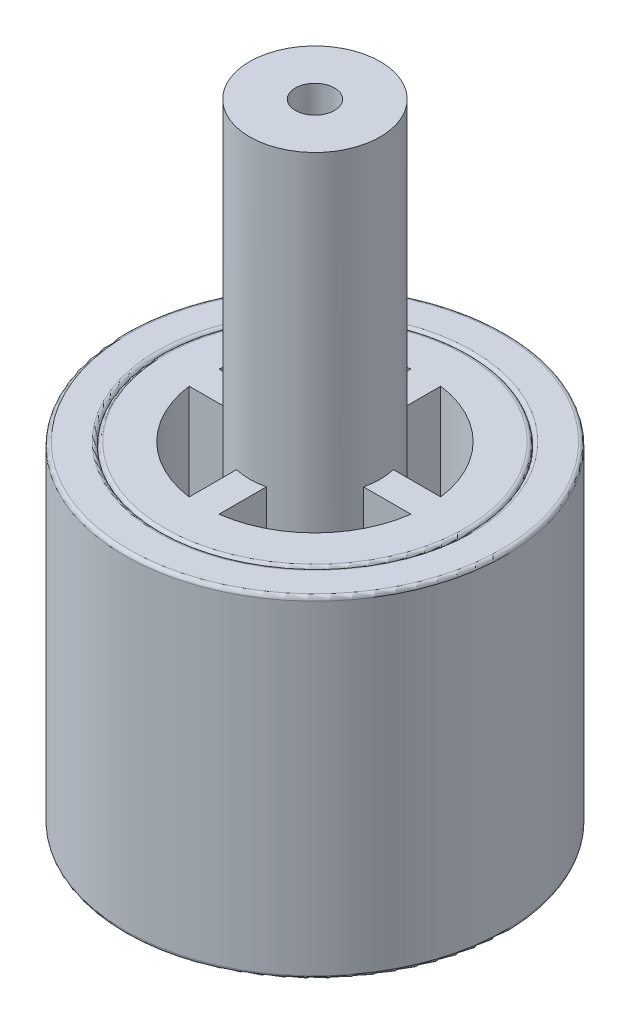
SolidWorks part; units mm, degrees
material "Полиамид ПА-6Б ТУ 6-05-988-93"
ref_plane "Спереди" through (0, 0, 0) normal (0, 0, 1) x (1, 0, 0)
ref_plane "Сверху" through (0, 0, 0) normal (0, 1, 0) x (1, 0, 0)
ref_plane "Справа" through (0, 0, 0) normal (1, 0, 0) x (0, 0, -1)
sketch "Эскиз1" plane through (0, 0, 0) normal (0, 1, 0) x (1, 0, 0)
  circle A0 centre (0, 0) radius 4.125
  dimension "D1" = 8.25
extrude "Бобышка-Вытянуть1" add sketch "Эскиз1" along normal blind 8.9
sketch "Эскиз2" plane through (0, 8.9, 0) normal (0, 1, 0) x (1, 0, 0)
  circle A0 centre (0, 0) radius 1.75
  dimension "D1" = 3.5
extrude "Бобышка-Вытянуть2" add sketch "Эскиз2" along normal blind 7.95
sketch "Эскиз3" plane through (0, 8.9, 0) normal (0, 1, 0) x (1, 0, 0)
  line L0 (-0.4, 2.9732) -> (-0.4, 1.7037)
  line L1 (-2.9732, 0.4) -> (-1.7037, 0.4)
  line L2 (-2.9732, -0.4) -> (-1.7037, -0.4)
  line L3 (0.4, 2.9732) -> (0.4, 1.7037)
  line L5 (1.7037, 0.4) -> (2.9732, 0.4)
  line L6 (1.7037, -0.4) -> (2.9732, -0.4)
  line L7 (0.4, -1.7037) -> (0.4, -2.9732)
  line L8 (-0.4, -1.7037) -> (-0.4, -2.9732)
  circle A0 centre (0, 0) radius 1.75 construction
  arc A1 (-0.4, 1.7037) -> (-1.7037, 0.4) centre (0, 0) ccw
  arc A2 (-0.4, 2.9732) -> (-2.9732, 0.4) centre (0, 0) ccw
  arc A3 (-1.7037, -0.4) -> (-0.4, -1.7037) centre (0, 0) ccw
  arc A4 (-2.9732, -0.4) -> (-0.4, -2.9732) centre (0, 0) ccw
  arc A5 (0.4, -1.7037) -> (1.7037, -0.4) centre (0, 0) ccw
  arc A6 (0.4, -2.9732) -> (2.9732, -0.4) centre (0, 0) ccw
  arc A7 (1.7037, 0.4) -> (0.4, 1.7037) centre (0, 0) ccw
  arc A8 (2.9732, 0.4) -> (0.4, 2.9732) centre (0, 0) ccw
  dimension "D1" = 6
  dimension "D2" = 0.4
  dimension "D3" = 0.8
  dimension "D4" = 0.4
  dimension "D5" = 0.8
extrude "Вырез-Вытянуть1" cut sketch "Эскиз3" against normal blind 3
sketch "Эскиз4" plane through (0, 0, 0) normal (0, -1, 0) x (1, 0, 0)
  line L2 (0.4, -1.7037) -> (0.4, -2.9732)
  line L3 (2.9732, -0.4) -> (1.7037, -0.4)
  line L4 (0.4, -1.7037) -> (0.4, -2.9732)
  line L5 (2.9732, -0.4) -> (1.7037, -0.4)
  line L6 (0.4, 2.9732) -> (0.4, 1.7037)
  line L7 (1.7037, 0.4) -> (2.9732, 0.4)
  line L8 (0.4, 2.9732) -> (0.4, 1.7037)
  line L9 (1.7037, 0.4) -> (2.9732, 0.4)
  line L10 (-2.9732, 0.4) -> (-1.7037, 0.4)
  line L11 (-0.4, 1.7037) -> (-0.4, 2.9732)
  line L12 (-2.9732, 0.4) -> (-1.7037, 0.4)
  line L13 (-0.4, 1.7037) -> (-0.4, 2.9732)
  line L14 (-1.7037, -0.4) -> (-2.9732, -0.4)
  line L15 (-0.4, -2.9732) -> (-0.4, -1.7037)
  line L16 (-1.7037, -0.4) -> (-2.9732, -0.4)
  line L17 (-0.4, -2.9732) -> (-0.4, -1.7037)
  arc A2 (0.4, -1.7037) -> (1.7037, -0.4) centre (0, 0) ccw
  arc A3 (0.4, -2.9732) -> (2.9732, -0.4) centre (0, 0) ccw
  arc A4 (0.4, -1.7037) -> (1.7037, -0.4) centre (0, 0) ccw
  arc A5 (0.4, -2.9732) -> (2.9732, -0.4) centre (0, 0) ccw
  arc A6 (2.9732, 0.4) -> (0.4, 2.9732) centre (0, 0) ccw
  arc A7 (1.7037, 0.4) -> (0.4, 1.7037) centre (0, 0) ccw
  arc A8 (2.9732, 0.4) -> (0.4, 2.9732) centre (0, 0) ccw
  arc A9 (1.7037, 0.4) -> (0.4, 1.7037) centre (0, 0) ccw
  arc A10 (-0.4, 1.7037) -> (-1.7037, 0.4) centre (0, 0) ccw
  arc A11 (-0.4, 2.9732) -> (-2.9732, 0.4) centre (0, 0) ccw
  arc A12 (-0.4, 1.7037) -> (-1.7037, 0.4) centre (0, 0) ccw
  arc A13 (-0.4, 2.9732) -> (-2.9732, 0.4) centre (0, 0) ccw
  arc A14 (-1.7037, -0.4) -> (-0.4, -1.7037) centre (0, 0) ccw
  arc A15 (-2.9732, -0.4) -> (-0.4, -2.9732) centre (0, 0) ccw
  arc A16 (-1.7037, -0.4) -> (-0.4, -1.7037) centre (0, 0) ccw
  arc A17 (-2.9732, -0.4) -> (-0.4, -2.9732) centre (0, 0) ccw
  dimension "D1" = 0
  dimension "D2" = 0
  dimension "D3" = 0
  dimension "D4" = 0
extrude "Вырез-Вытянуть2" cut sketch "Эскиз4" against normal blind 3
sketch "Эскиз5" plane through (0, 0, 0) normal (0, -1, 0) x (1, 0, 0)
  circle A0 centre (0, 0) radius 0.525
  dimension "D1" = 1.05
extrude "Вырез-Вытянуть3" cut sketch "Эскиз5" against normal up to surface (16.85 mm away) up to face at (0, 16.85, 1.75)
sketch "Эскиз6" plane through (0, 8.9, 0) normal (0, 1, 0) x (1, 0, 0)
  circle A0 centre (0, 0) radius 4.125 construction
  circle A1 centre (0, 0) radius 4.125
  circle A2 centre (0, 0) radius 5.1
  dimension "D1" = 10.2
extrude "Бобышка-Вытянуть3" add sketch "Эскиз6" against normal up to surface (8.9 mm away) separate body up to face at (0, 0, -0.525)
fillet "Скругление1" radius 0.1 4 edges at (0, 0, 4.125) (0, 0, 5.1) (0, 8.9, 4.125) (0, 8.9, 5.1)
fillet "Скругление2" radius 0.1 2 edges at (0, 0, 4.125) (0, 8.9, 4.125)
